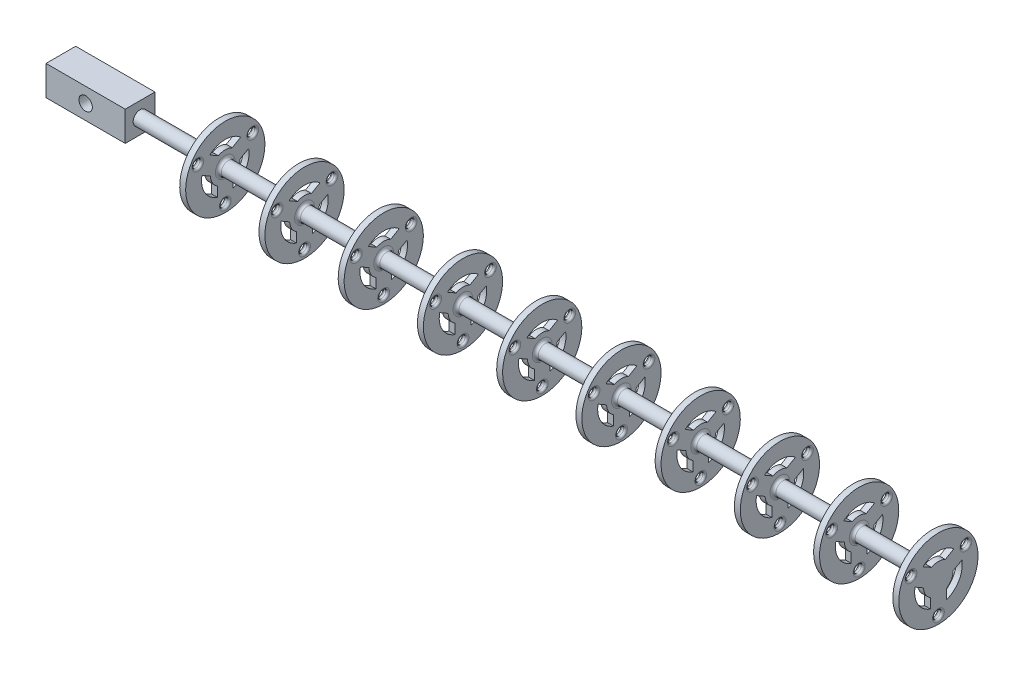
SolidWorks part; units mm, degrees
ref_plane "Front Plane" through (0, 0, 0) normal (0, 0, 1) x (1, 0, 0)
ref_plane "Top Plane" through (0, 0, 0) normal (0, 1, 0) x (1, 0, 0)
ref_plane "Right Plane" through (0, 0, 0) normal (1, 0, 0) x (0, 0, -1)
sketch "Sketch2" plane through (0, 0, 0) normal (0, 0, 1) x (1, 0, 0)
  line L0 (0, 1.75) -> (200, 1.75)
  line L1 (0, -11) -> (0, 11) construction
  line L2 (200, 1.75) -> (200, 0)
  line L3 (200, 0) -> (0, 0)
  line L4 (0, 0) -> (0, 1.75)
  dimension "D1" = 1.75
  dimension "D2" = 200
  dimension "D3" = 1.75
revolve "Revolve1" add sketch "Sketch2" angle 360 about L3
ref_axis "Axis1" through (-3.9062, 0, 0) along (1, 0, 0)
sketch "Sketch3" plane through (0, 0, 0) normal (0, 0, 1) x (1, 0, 0)
  line L0 (20, 0) -> (20, 10)
  line L1 (20, 10) -> (21.5, 10)
  line L2 (21.5, 10) -> (21.5, 0)
  line L3 (21.5, 0) -> (20, 0)
  line L4 (0, -11) -> (0, 11) construction
  dimension "D1" = 1.5
  dimension "D2" = 10
  dimension "D3" = 20
revolve "Revolve2" add sketch "Sketch3" angle 360 about L3
sketch "Sketch5" plane through (21.5, 0, 0) normal (1, 0, 0) x (0, 0, -1)
  line L0 (0, -8) -> (0, 0) construction
  line L1 (0, 0) -> (6.9282, 4) construction
  line L2 (-6.9282, 4) -> (0, 0) construction
  line L3 (0, 11) -> (0, -11) construction
  line L4 (-3.899, 4.5605) -> (-1.7472, 3.3181)
  line L5 (1.7472, 3.3181) -> (3.899, 4.5605)
  line L6 (2, -3.1721) -> (2, -5.6569)
  line L7 (5.899, 1.0964) -> (3.7472, -0.146)
  line L8 (-3.7472, -0.146) -> (-5.899, 1.0964)
  line L9 (-2, -5.6569) -> (-2, -3.1721)
  circle A0 centre (0, -8) radius 1
  circle A1 centre (6.9282, 4) radius 1
  circle A2 centre (-6.9282, 4) radius 1
  arc A3 (-3.899, 4.5605) -> (3.899, 4.5605) centre (0, 0) cw
  circle A6 centre (0, 0) radius 10 construction
  arc A8 (-1.7472, 3.3181) -> (1.7472, 3.3181) centre (0, 0) cw
  circle A9 centre (0, 0) radius 1.75 construction
  arc A10 (5.899, 1.0964) -> (2, -5.6569) centre (0, 0) cw
  arc A11 (3.7472, -0.146) -> (2, -3.1721) centre (0, 0) cw
  arc A12 (-2, -5.6569) -> (-5.899, 1.0964) centre (0, 0) cw
  arc A13 (-2, -3.1721) -> (-3.7472, -0.146) centre (0, 0) cw
  point P29 (0, 0)
  dimension "D2" = 2
  dimension "D1" = 8
  dimension "D3" = 120
  dimension "D4" = 120
  dimension "D6" = 2
  dimension "D7" = 4
  dimension "D5" = 2
  dimension "D8" = 3
extrude "Cut-Extrude1" cut sketch "Sketch5" against normal up to next
fillet "Fillet1" radius 0.5 6 edges at (20, 3, -6.9282) (20, -9, 0) (21.5, -7, 0) (21.5, 5, -6.9282) (20, 3, 6.9282) (21.5, 5, 6.9282)
pattern_linear "LPattern1" count 10 spacing 20 along (1, 0, 0) of "Revolve2", "Cut-Extrude1", "Fillet1"
sketch "Sketch16" plane through (0, 0, 0) normal (-1, 0, 0) x (0, 0, 1)
  line L1 (-3.75, -3.75) -> (3.75, -3.75)
  line L2 (-3.75, -3.75) -> (-3.75, 3.75)
  line L3 (-3.75, 3.75) -> (3.75, 3.75)
  line L4 (3.75, -3.75) -> (3.75, 3.75)
  line L5 (-3.75, -3.75) -> (3.75, 3.75) construction
  line L6 (-3.75, 3.75) -> (3.75, -3.75) construction
  point P0 (0, 0)
  dimension "D1" = 7.5
extrude "Boss-Extrude1" add sketch "Sketch16" along normal blind 20
sketch "Sketch19" plane through (0, 0, -3.75) normal (0, 0, -1) x (-1, 0, 0)
  line L0 (3.9062, 0) -> (-200, 0) construction
  line L1 (20, 3.75) -> (0, 3.75) construction
  line L2 (20, 3.75) -> (20, -3.75) construction
  point P0 (10, 0)
  point P7 (10, 3.75)
  point P10 (20, 0)
hole_wizard "M3 Clearance Hole1" positions "Sketch19" profile "Sketch18" hole size "M3" standard "ANSI Metric" end condition through all
sketch "Sketch18" plane through (-10, 0, -3.75) normal (1, 0, 0) x (0, 1, 0)
  line L0 (0, 0) -> (0, 13.75)
  line L1 (0, 13.75) -> (1.7, 13.75)
  line L2 (1.7, 13.75) -> (1.7, 0.025)
  line L3 (1.7, 0.025) -> (1.725, 0)
  line L5 (1.725, 0) -> (0, 0)
  line L6 (-1.7, 0.025) -> (-1.725, 0) construction
  line L11 (0, -6.35) -> (0, 107.95) construction
  dimension "Thru Hole Dia." = 3.4
  dimension "Thru Hole Depth" = 13.75
  dimension "Near C'Sink Dia." = 3.45
  dimension "Near C'Sink Angle" = 90
fillet "Fillet2" radius 0.75 19 edges at (20, -1.75, 0) (21.5, 1.75, 0) (40, -1.75, 0) (41.5, 1.75, 0) (60, -1.75, 0) (61.5, 1.75, 0) (80, -1.75, 0) (81.5, 1.75, 0) (100, -1.75, 0) (101.5, 1.75, 0) (120, -1.75, 0) (121.5, 1.75, 0) (140, -1.75, 0) (141.5, 1.75, 0) (160, -1.75, 0) (161.5, 1.75, 0) (180, -1.75, 0) (181.5, 1.75, 0) (200, 1.75, 0)
equation "\"R_initial\"= 1.75"
equation "\"D1@Sketch2\"=\"R_initial\""
equation "\"R_distal\"= 1.75"
equation "\"D3@Sketch2\"=\"R_distal\""
equation "\"L\"=200"
equation "\"D2@Sketch2\"=\"L\""
equation "\"disk_thickness\"= 1.5"
equation "\"D1@Sketch3\"=\"disk_thickness\""
equation "\"disk_radius\"= 10"
equation "\"D2@Sketch3\"=\"disk_radius\""
equation "\"disk_spacing_initial\"= 20"
equation "\"D3@Sketch3\"=\"disk_spacing_initial\""
equation "\"tendon_routing_radius\"= 8"
equation "\"D1@Sketch5\"=\"tendon_routing_radius\""
equation "\"tendon_routing_hole_radius\"=2"
equation "\"D2@Sketch5\"=\"tendon_routing_hole_radius\""
equation "\"tendon_routing_hole_fillet\"=0.5"
equation "\"D1@Fillet1\"=\"tendon_routing_hole_fillet\""
equation "\"inter_disk_spacing\"= 20"
equation "\"D3@LPattern1\"=\"inter_disk_spacing\""
equation "\"num_disk\"= 10"
equation "\"D1@LPattern1\"=\"num_disk\""
